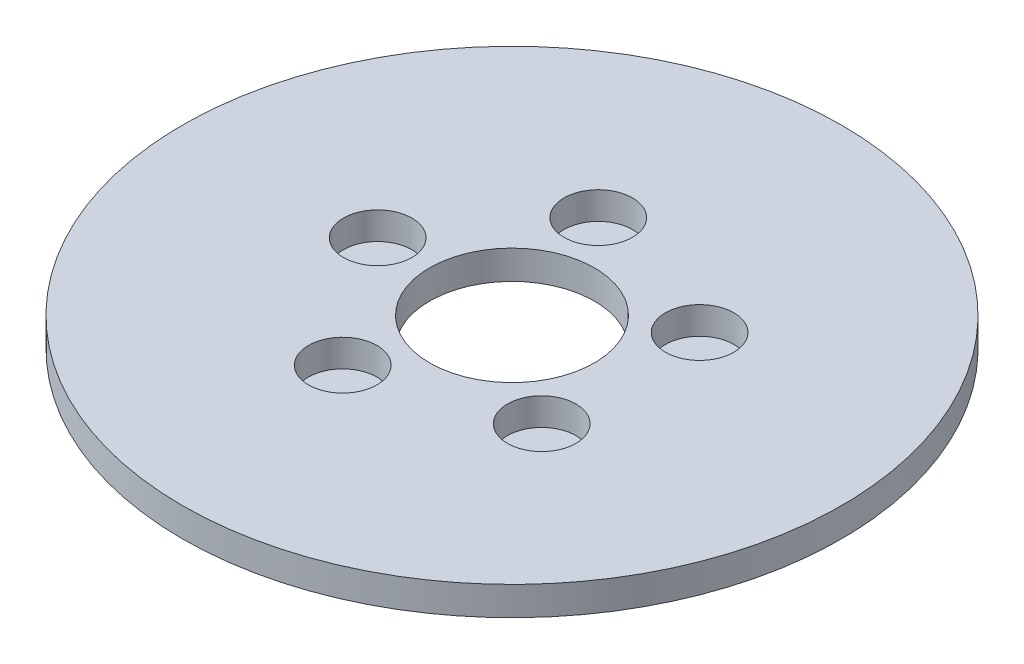
SolidWorks part; units mm, degrees
ref_plane "Front Plane" through (0, 0, 0) normal (0, 0, 1) x (1, 0, 0)
ref_plane "Top Plane" through (0, 0, 0) normal (0, 1, 0) x (1, 0, 0)
ref_plane "Right Plane" through (0, 0, 0) normal (1, 0, 0) x (0, 0, -1)
sketch "Sketch1" plane through (0, 0, 0) normal (0, 1, 0) x (1, 0, 0)
  circle A0 centre (0, 0) radius 80
  dimension "FLANGE_OD" = 160
extrude "Boss-Extrude1" add sketch "Sketch1" along normal blind 7
sketch "Sketch2" plane through (0, 0, 0) normal (0, 1, 0) x (1, 0, 0)
  circle A0 centre (0, 0) radius 20
  dimension "BORE_D" = 40
extrude "Cut-Extrude1" cut sketch "Sketch2" along normal through all
sketch "Sketch3" plane through (0, 7, 0) normal (0, 1, 0) x (1, 0, 0)
  circle A0 centre (0, 0) radius 32.6105 construction
  circle A1 centre (-32.6105, 0) radius 8.3061
  dimension "BOLT_D" = 16.6121
  dimension "BOLT_PCD" = 65.2211
extrude "Cut-Extrude2" cut sketch "Sketch3" against normal blind 6.6581
pattern_circular "CirPattern1" count 5 over 360 about axis through (0, 0, 0) along (0, 1, 0) of "Cut-Extrude2"
